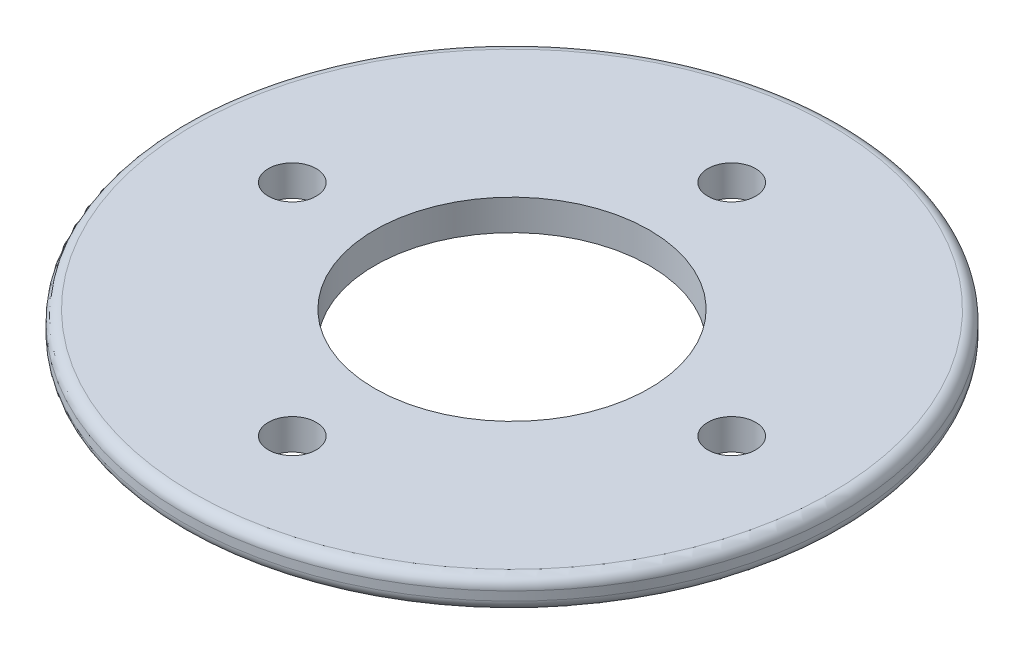
SolidWorks part; units mm, degrees
ref_plane "Front" through (0, 0, 0) normal (0, 0, 1) x (1, 0, 0)
ref_plane "Top" through (0, 0, 0) normal (0, 1, 0) x (1, 0, 0)
ref_plane "Right" through (0, 0, 0) normal (1, 0, 0) x (0, 0, -1)
sketch "Sketch1" plane through (0, 0, 0) normal (0, 1, 0) x (1, 0, 0)
  circle A0 centre (0, 0) radius 15
  dimension "D1" = 30
extrude "Boss-Extrude1" add sketch "Sketch1" along normal blind 1.4
sketch "Sketch2" plane through (0, 1.4, 0) normal (0, 1, 0) x (1, 0, 0)
  line L0 (0, 0) -> (0, 15) construction
  circle A0 centre (0, 0) radius 15 construction
  circle A1 centre (0, 10) radius 1.09
  dimension "D1" = 2.18
  dimension "D2" = 10
extrude "Cut-Extrude1" cut sketch "Sketch2" against normal up to surface (1.4 mm away) up to face at (0, 0, 15)
sketch "Sketch3" plane through (0, 1.4, 0) normal (0, 1, 0) x (1, 0, 0)
  point P0 (0, 0)
sketch "Sketch4" plane through (0, 0, 0) normal (0, 0, 1) x (1, 0, 0)
  line L0 (0, 0) -> (0, 1.4) construction
pattern_circular "CirPattern1" count 4 over 360 about axis through (0, 0, 0) along (0, 1, 0) of "Cut-Extrude1"
fillet "Fillet1" radius 0.5 2 edges at (0, 0, 15) (0, 1.4, 15)
sketch "Sketch5" plane through (0, 1.4, 0) normal (0, 1, 0) x (1, 0, 0)
  circle A0 centre (0, 0) radius 6.25
  dimension "D1" = 12.5
extrude "Cut-Extrude2" cut sketch "Sketch5" against normal mid plane 50
